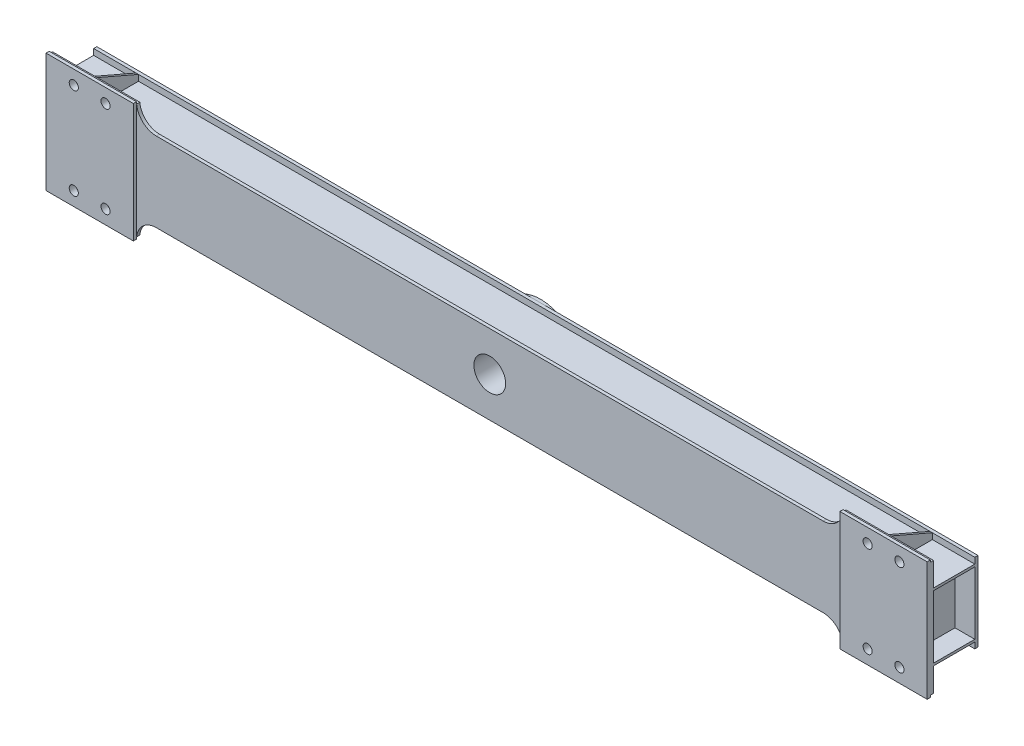
SolidWorks part; units mm, degrees
ref_plane "前视基准面" through (0, 0, 0) normal (0, 0, 1) x (1, 0, 0)
ref_plane "上视基准面" through (0, 0, 0) normal (0, 1, 0) x (1, 0, 0)
ref_plane "右视基准面" through (0, 0, 0) normal (1, 0, 0) x (0, 0, -1)
sketch "草图1" plane through (0, 0, 0) normal (0, 0, 1) x (1, 0, 0)
  line L1 (0, 0) -> (2220, 0)
  line L2 (0, 0) -> (0, 300)
  line L3 (0, 300) -> (2220, 300)
  line L4 (2220, 0) -> (2220, 300)
  dimension "D1" = 2220
  dimension "D2" = 300
extrude "凸台-拉伸1" add sketch "草图1" along normal blind 120
sketch "草图2" plane through (0, 0, 120) normal (0, 0, 1) x (1, 0, 0)
  line L0 (2220, 300) -> (0, 300) construction
  line L1 (220, 300) -> (2000, 300)
  line L2 (220, 300) -> (220, 250)
  line L3 (220, 250) -> (2000, 250)
  line L4 (2000, 300) -> (2000, 250)
  line L5 (0, 0) -> (2220, 0) construction
  line L6 (220, 50) -> (2000, 50)
  line L7 (220, 50) -> (220, 0)
  line L8 (220, 0) -> (2000, 0)
  line L9 (2000, 50) -> (2000, 0)
  line L10 (0, 300) -> (0, 0) construction
  line L11 (2220, 0) -> (2220, 300) construction
  dimension "D1" = 220
  dimension "D2" = 220
  dimension "D3" = 50
  dimension "D4" = 50
extrude "切除-拉伸1" cut sketch "草图2" against normal through all
sketch "草图3" plane through (0, 0, 120) normal (0, 0, 1) x (1, 0, 0)
  line L0 (0, 0) -> (220, 0) construction
  line L1 (0, 300) -> (220, 300)
  line L2 (0, 300) -> (0, 0)
  line L3 (0, 0) -> (220, 0)
  line L4 (220, 300) -> (220, 0)
  line L5 (220, 50) -> (220, 0) construction
  line L7 (2000, 300) -> (2220, 300)
  line L8 (2000, 300) -> (2000, 0)
  line L9 (2000, 0) -> (2220, 0)
  line L10 (2220, 300) -> (2220, 0)
extrude "凸台-拉伸2" add sketch "草图3" along normal blind 8
sketch "草图4" plane through (0, 300, 0) normal (0, 1, 0) x (1, 0, 0)
  line L0 (0, -128) -> (0, 0) construction
  line L1 (2220, 0) -> (0, 0)
  line L2 (2220, 0) -> (2220, -120)
  line L3 (2220, -120) -> (0, -120)
  line L4 (0, 0) -> (0, -120)
  line L5 (220, -120) -> (2000, -120) construction
extrude "切除-拉伸2" cut sketch "草图4" against normal blind 5
sketch "草图5" plane through (0, 0, 0) normal (0, -1, 0) x (1, 0, 0)
  line L0 (2220, 128) -> (2220, 0) construction
  line L1 (0, 0) -> (2220, 0)
  line L2 (0, 0) -> (0, 120)
  line L3 (0, 120) -> (2220, 120)
  line L4 (2220, 0) -> (2220, 120)
  line L5 (2000, 120) -> (220, 120) construction
extrude "切除-拉伸3" cut sketch "草图5" against normal blind 5
sketch "草图13" plane through (2220, 0, 0) normal (1, 0, 0) x (0, 0, -1)
  line L0 (-128, 150) -> (0, 150) construction
  line L1 (-128, 0) -> (-128, 300) construction
  line L2 (0, 5) -> (0, 295) construction
  line L4 (-112, 235) -> (-8, 235)
  line L5 (-112, 235) -> (-112, 295)
  line L6 (-112, 295) -> (0, 295)
  line L7 (-8, 235) -> (-8, 250)
  line L8 (-120, 295) -> (-120, 300) construction
  line L9 (-8, 250) -> (0, 250)
  line L10 (0, 250) -> (0, 295)
  line L12 (-120, 295) -> (0, 295) construction
  line L13 (-112, 5) -> (0, 5)
  line L14 (0, 5) -> (-120, 5) construction
  line L15 (0, 5) -> (0, 50)
  line L16 (0, 50) -> (-8, 50)
  line L17 (-8, 50) -> (-8, 65)
  line L18 (-8, 65) -> (-112, 65)
  line L19 (-112, 5) -> (-112, 65)
  point P14 (-120, 297.5)
  dimension "D1" = 85
  dimension "D2" = 8
  dimension "D3" = 100
  dimension "D4" = 8
extrude "切除-拉伸11" cut sketch "草图13" against normal through all
sketch "草图14" plane through (0, 235, 0) normal (0, 1, 0) x (1, 0, 0)
  line L0 (0, -8) -> (2220, -8) construction
  line L1 (2107, -8) -> (2113, -8)
  line L2 (2107, -8) -> (2107, -112)
  line L3 (2107, -112) -> (2113, -112)
  line L4 (2113, -8) -> (2113, -112)
  line L5 (0, -112) -> (2220, -112) construction
  line L6 (2220, -8) -> (2220, -112) construction
  point P8 (2220, -60)
  dimension "D1" = 6
  dimension "D2" = 107
extrude "凸台-拉伸3" add sketch "草图14" along normal blind 60
sketch "草图16" plane through (0, 65, 0) normal (0, -1, 0) x (1, 0, 0)
  line L0 (0, 112) -> (2220, 112) construction
  line L1 (2107, 112) -> (2113, 112)
  line L2 (2107, 112) -> (2107, 8)
  line L3 (2107, 8) -> (2113, 8)
  line L4 (2113, 112) -> (2113, 8)
  line L5 (0, 8) -> (2220, 8) construction
  line L7 (2220, 8) -> (2220, 112) construction
  dimension "D1" = 6
  dimension "D2" = 107
extrude "凸台-拉伸4" add sketch "草图16" along normal blind 60
sketch "草图15" plane through (2113, 0, 0) normal (1, 0, 0) x (0, 0, -1)
  line L0 (-8, 295) -> (-8, 250)
  line L1 (-8, 250) -> (-112, 295)
  line L2 (-112, 295) -> (-8, 295)
  line L3 (-8, 50) -> (-112, 5)
  line L4 (-112, 5) -> (-8, 5)
  line L5 (-8, 5) -> (-8, 50)
extrude "切除-拉伸12" cut sketch "草图15" against normal through all
pattern_linear "阵列(线性)2" count 2 spacing 2000 along (-1, 0, 0) of "凸台-拉伸3", "凸台-拉伸4", "切除-拉伸12"
fillet "圆角3" radius 50 4 edges at (2000, 250, 116) (2000, 50, 116)
sketch "草图17" plane through (0, 0, 0) normal (-1, 0, 0) x (0, 0, 1)
  line L0 (8, 235) -> (112, 235) construction
  line L1 (8, 229) -> (112, 229)
  line L2 (8, 229) -> (8, 71)
  line L3 (8, 71) -> (112, 71)
  line L4 (112, 229) -> (112, 71)
  line L5 (112, 65) -> (8, 65) construction
  line L7 (8, 235) -> (8, 250) construction
  line L8 (112, 295) -> (112, 235) construction
  dimension "D1" = 6
  dimension "D2" = 6
extrude "切除-拉伸13" cut sketch "草图17" against normal blind 50
sketch "草图18" plane through (2220, 0, 0) normal (1, 0, 0) x (0, 0, -1)
  line L0 (-112, 235) -> (-8, 235) construction
  line L1 (-112, 229) -> (-8, 229)
  line L2 (-112, 229) -> (-112, 71)
  line L3 (-112, 71) -> (-8, 71)
  line L4 (-8, 229) -> (-8, 71)
  line L5 (-8, 65) -> (-112, 65) construction
  line L6 (-112, 295) -> (-112, 235) construction
  line L7 (-8, 250) -> (-8, 235) construction
  dimension "D1" = 6
  dimension "D2" = 6
extrude "切除-拉伸14" cut sketch "草图18" against normal blind 50
sketch "草图19" plane through (0, 0, 0) normal (0, 0, -1) x (-1, 0, 0)
  line L0 (-1110, 250) -> (-1110, 50) construction
  line L1 (0, 250) -> (-2220, 250) construction
  line L2 (-2220, 50) -> (0, 50) construction
  circle A0 centre (-1110, 150) radius 100
  dimension "D1" = 200
extrude "凸台-拉伸5" add sketch "草图19" along normal blind 8
sketch "草图20" plane through (0, 0, -8) normal (0, 0, -1) x (-1, 0, 0)
  circle A0 centre (-1110, 150) radius 40
  circle A1 centre (-1110, 150) radius 100 construction
  dimension "D1" = 80
extrude "切除-拉伸15" cut sketch "草图20" against normal through all
sketch "草图21" plane through (0, 0, 128) normal (0, 0, 1) x (1, 0, 0)
  line L0 (2220, 150) -> (0, 150) construction
  line L1 (2220, 0) -> (2220, 300) construction
  line L2 (0, 300) -> (0, 0) construction
  line L3 (2110, 0) -> (2110, 300) construction
  line L4 (2000, 0) -> (2220, 0) construction
  line L5 (2220, 300) -> (2000, 300) construction
  circle A0 centre (2150, 35) radius 11.5
  dimension "D1" = 23
  dimension "D2" = 40
  dimension "D3" = 115
extrude "切除-拉伸16" cut sketch "草图21" against normal through all
pattern_linear "阵列(线性)3" count 2 spacing 80 along (-1, 0, 0) count 2 spacing 230 along (0, 1, 0) of "切除-拉伸16"
pattern_linear "阵列(线性)4" count 2 spacing 2000 along (-1, 0, 0) of "切除-拉伸16", "阵列(线性)3"
sketch "草图22" plane through (0, 0, 0) normal (0, 0, -1) x (-1, 0, 0)
  line L0 (-2220, 150) -> (0, 150) construction
  line L1 (-2220, 50) -> (-2220, 250) construction
  line L2 (0, 250) -> (0, 50) construction
  line L3 (-2110, 300) -> (-2110, 0) construction
  line L4 (-2000, 300) -> (-2220, 300) construction
  line L5 (-2220, 0) -> (-2000, 0) construction
  circle A0 centre (-2150, 190) radius 5
  dimension "D1" = 10
  dimension "D2" = 40
  dimension "D3" = 40
extrude "切除-拉伸17" cut sketch "草图22" against normal blind 100
pattern_linear "阵列(线性)5" count 2 spacing 80 along (-1, 0, 0) count 2 spacing 80 along (0, -1, 0) of "切除-拉伸17"
pattern_linear "阵列(线性)6" count 2 spacing 2000 along (-1, 0, 0) of "切除-拉伸17", "阵列(线性)5"
